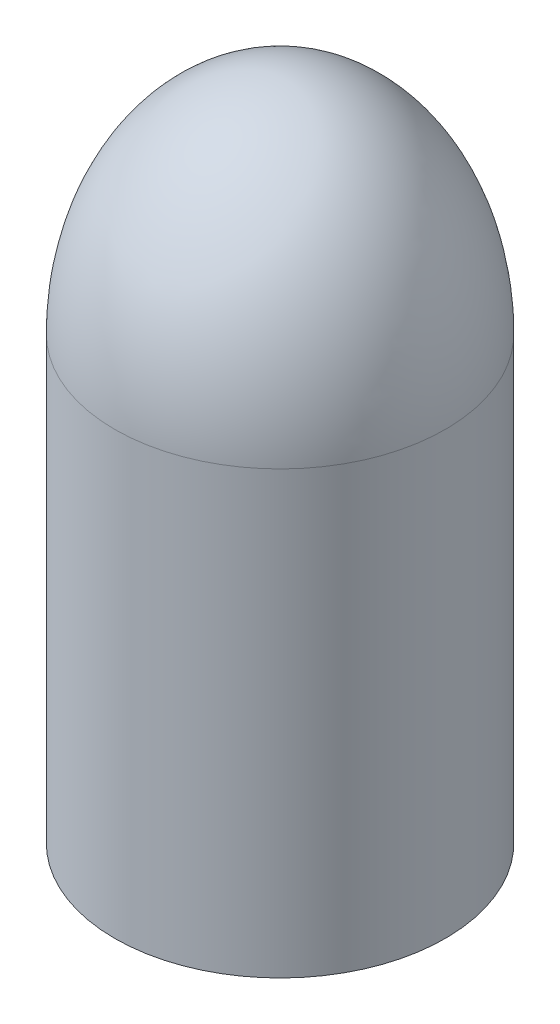
SolidWorks part; units mm, degrees
ref_plane "Piano frontale" through (0, 0, 0) normal (0, 0, 1) x (1, 0, 0)
ref_plane "Piano superiore" through (0, 0, 0) normal (0, 1, 0) x (1, 0, 0)
ref_plane "Piano destro" through (0, 0, 0) normal (1, 0, 0) x (0, 0, -1)
sketch "Schizzo2" plane through (0, 0, 0) normal (0, 1, 0) x (1, 0, 0)
  circle A0 centre (0, 0) radius 1.5
  dimension "D1" = 3
extrude "Estrusione-Estrusione1" add sketch "Schizzo2" along normal blind 4
dome "Cupola1" faces to dome 1 distance 2 reverse direction no elliptical dome yes face at (0, 4, 1.5) parameters "D1"=2
ref_axis "Assi1" through (0, 4.4035, 0) along (0, -1, 0)
